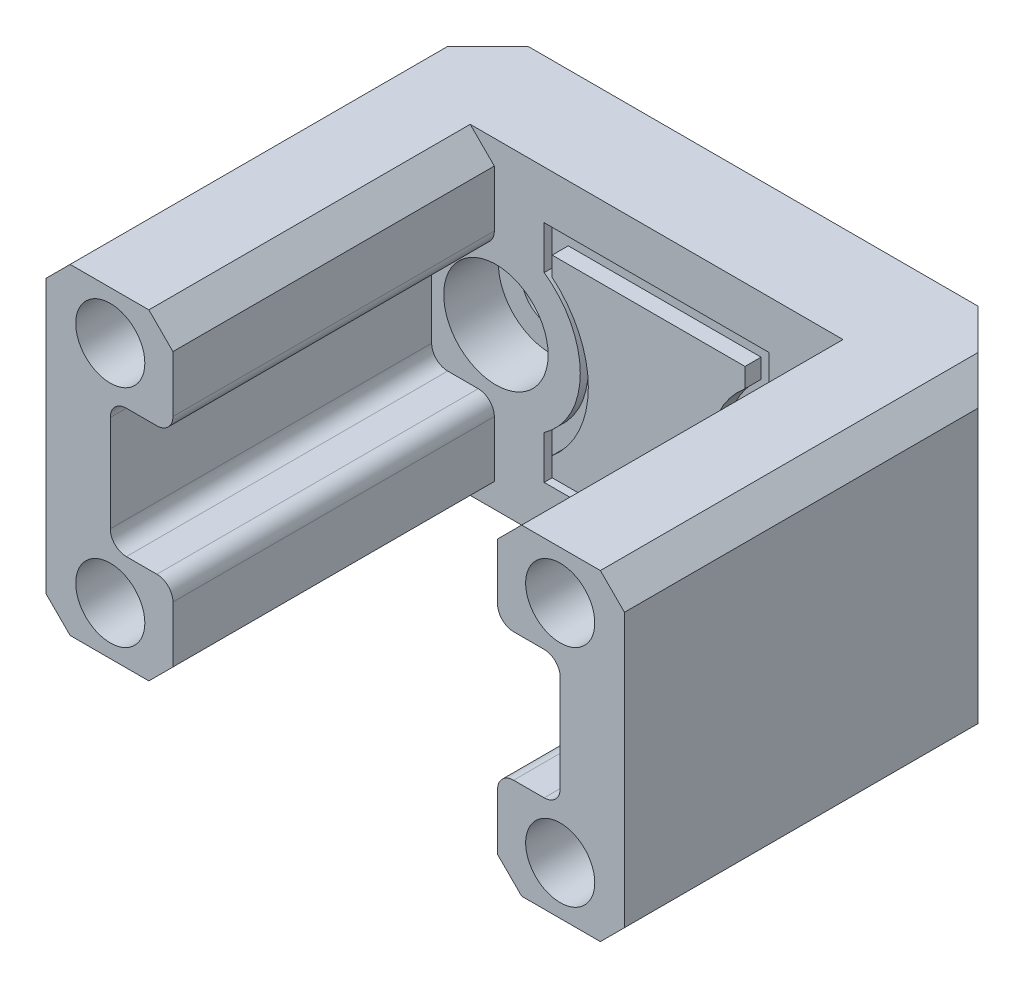
SolidWorks part; units mm, degrees
material "PETG"
ref_plane "Płaszczyzna przednia" through (0, 0, 0) normal (0, 0, 1) x (1, 0, 0)
ref_plane "Płaszczyzna górna" through (0, 0, 0) normal (0, 1, 0) x (1, 0, 0)
ref_plane "Płaszczyzna prawa" through (0, 0, 0) normal (1, 0, 0) x (0, 0, -1)
sketch "Sketch1" plane through (0, 0, 0) normal (0, 0, 1) x (1, 0, 0)
  line L1 (0, 0) -> (28, 0)
  line L2 (0, 0) -> (0, 20)
  line L3 (0, 20) -> (28, 20)
  line L4 (28, 0) -> (28, 20)
  dimension "D1" = 20
  dimension "D2" = 28
extrude "Boss-Extrude1" add sketch "Sketch1" along normal blind 6
hole_wizard "CBORE for M3 Hex Socket Head Cap Screw1" positions "Sketch2" profile "Sketch4" counterbore size "M3" standard "DIN" end condition through all
sketch "Sketch2" plane through (0, 0, 6) normal (0, 0, 1) x (1, 0, 0)
  line L1 (0, 10) -> (4, 10) construction
  line L2 (0, 20) -> (0, 0) construction
  line L3 (4, 10) -> (24, 10) construction
  line L5 (28, 10) -> (24, 10) construction
  line L6 (28, 0) -> (28, 20) construction
  point P0 (4, 10)
  point P2 (24, 10)
  dimension "D1" = 20
sketch "Sketch4" plane through (4, 10, 6) normal (1, 0, 0) x (0, -1, 0)
  line L0 (0, 0) -> (0, 6)
  line L1 (0, 6) -> (1.8, 6)
  line L3 (1.8, 6) -> (1.8, 3.4)
  line L4 (1.8, 3.4) -> (3.25, 3.4)
  line L5 (3.25, 3.4) -> (3.25, 0)
  line L7 (3.25, 0) -> (0, 0)
  line L11 (0, -6.35) -> (0, 107.95) construction
  dimension "Thru Hole Dia." = 3.6
  dimension "Thru Hole Depth" = 6
  dimension "C'Bore Dia." = 6.5
  dimension "C'Bore Depth" = 3.4
sketch "Sketch5" plane through (0, 0, 6) normal (0, 0, 1) x (1, 0, 0)
  line L0 (24.1, 20) -> (24.1, 14)
  line L1 (0, 20) -> (3.9, 20)
  line L2 (0, 20) -> (0, 14)
  line L3 (0, 14) -> (3.9, 14)
  line L4 (3.9, 20) -> (3.9, 14)
  line L9 (24.1, 20) -> (28, 20)
  line L10 (28, 20) -> (28, 14)
  line L11 (24.1, 14) -> (28, 14)
  line L12 (24.1, 6) -> (24.1, 0)
  line L13 (24.1, 6) -> (28, 6)
  line L14 (28, 6) -> (28, 0)
  line L15 (24.1, 0) -> (28, 0)
  line L16 (0, 6) -> (0, 0)
  line L17 (0, 6) -> (3.9, 6)
  line L18 (3.9, 6) -> (3.9, 0)
  line L19 (0, 0) -> (3.9, 0)
  line L20 (28, 0) -> (28, 20) construction
  line L21 (0, 0) -> (28, 0) construction
  dimension "D1" = 20.2
  dimension "D2" = 6
  dimension "D3" = 2
  dimension "D4" = 2
extrude "Boss-Extrude2" add sketch "Sketch5" along normal blind 20
sketch "Sketch6" plane through (0, 0, 0) normal (0, 0, -1) x (-1, 0, 0)
  line L0 (-28, 20) -> (0, 20) construction
  line L1 (-28, 20) -> (-32, 20)
  line L2 (-28, 20) -> (-28, 0)
  line L3 (-28, 0) -> (-32, 0)
  line L4 (-32, 20) -> (-32, 0)
  line L5 (0, 0) -> (4, 0)
  line L6 (0, 0) -> (0, 20)
  line L7 (0, 20) -> (4, 20)
  line L8 (4, 0) -> (4, 20)
  line L9 (0, 0) -> (-28, 0) construction
  dimension "D1" = 4
extrude "Boss-Extrude3" add sketch "Sketch6" against normal up to surface (26 mm away) up to face at (26.05, 17, 26)
fillet "Fillet1" radius 1 8 edges at (0, 14, 16) (0, 6, 16) (28, 14, 16) (28, 6, 16) (3.9, 14, 16) (3.9, 6, 16) (24.1, 14, 16) (24.1, 6, 16)
hole_wizard "Ø4.3 (4.3) Diameter Hole1" positions "Sketch7" profile "Sketch8" hole size "Ø4.3" standard "DIN"
sketch "Sketch7" plane through (0, 0, 26) normal (0, 0, 1) x (1, 0, 0)
  line L1 (-4, 20) -> (0, 20) construction
  line L2 (-4, 20) -> (-4, 17) construction
  line L3 (-4, 17) -> (0, 17) construction
  line L4 (0, 20) -> (0, 17) construction
  line L5 (14, 20) -> (14, 2.3578)
  line L6 (24.1, 20) -> (3.9, 20) construction
  line L8 (-4, 10) -> (16.4891, 10)
  line L9 (-4, 20) -> (-4, 0) construction
  point P1 (0, 17)
  point P60 (0, 3)
  point P62 (28, 3)
  point P63 (28, 17)
  dimension "D1" = 3
  dimension "D2" = 4
sketch "Sketch8" plane through (28, 17, 26) normal (1, 0, 0) x (0, -1, 0)
  line L0 (0, 0) -> (0, 11.2919)
  line L1 (0, 11.2919) -> (2.15, 10)
  line L2 (2.15, 10) -> (2.15, 0)
  line L5 (2.15, 0) -> (0, 0)
  line L10 (0, 11.2919) -> (-2.15, 10) construction
  line L11 (0, -6.35) -> (0, 107.95) construction
  dimension "Hole Dia." = 4.3
  dimension "Hole Depth" = 10
  dimension "Drill Angle" = 118
chamfer "Chamfer1" distance 1.5 angle 45 8 edges at (24.1, 20, 16) (24.1, 0, 16) (3.9, 20, 16) (3.9, 0, 16) (-4, 0, 13) (-4, 20, 13) (32, 0, 13) (32, 20, 13)
sketch "Sketch9" plane through (0, 0, 6) normal (0, 0, 1) x (1, 0, 0)
  line L0 (14, 17) -> (14, 20) construction
  line L1 (7, 17) -> (21, 17)
  line L2 (7, 17) -> (7, 3)
  line L3 (7, 3) -> (21, 3)
  line L4 (21, 17) -> (21, 3)
  line L5 (25.6, 20) -> (2.4, 20) construction
  line L6 (7, 10) -> (-4, 10) construction
  line L7 (-4, 18.5) -> (-4, 1.5) construction
  circle A0 centre (24, 10) radius 3.25 construction
  circle A1 centre (4, 10) radius 3.25 construction
  circle A2 centre (24, 10) radius 3.25
  circle A3 centre (4, 10) radius 3.25
  circle A4 centre (4, 10) radius 5.25
  circle A5 centre (24, 10) radius 5.25
  dimension "D2" = 14
  dimension "D3" = 14
  dimension "D1" = 2
extrude "Cut-Extrude1" cut sketch "Sketch9" against normal blind 0.5 contours A5 L4 L1 L2 A4 L3 region at (14, 10, 6)
sketch "Sketch10" plane through (0, 0, 5.5) normal (0, 0, 1) x (1, 0, 0)
  line L0 (20, 4) -> (20, 5.1977)
  line L1 (8, 4) -> (20, 4)
  line L2 (8, 5.1977) -> (8, 4)
  line L3 (8, 16) -> (8, 14.8023)
  line L4 (20, 16) -> (8, 16)
  line L5 (20, 14.8023) -> (20, 16)
  line L6 (21, 14.3084) -> (21, 17)
  line L7 (21, 17) -> (7, 17)
  line L8 (7, 17) -> (7, 14.3084)
  line L9 (7, 5.6916) -> (7, 3)
  line L10 (7, 3) -> (21, 3)
  line L11 (21, 3) -> (21, 5.6916)
  line L12 (21, 14.3084) -> (21, 17)
  line L13 (21, 17) -> (7, 17)
  line L14 (7, 17) -> (7, 14.3084)
  line L15 (7, 5.6916) -> (7, 3)
  line L16 (7, 3) -> (21, 3)
  line L17 (21, 3) -> (21, 5.6916)
  arc A0 (20, 14.8023) -> (20, 5.1977) centre (24, 10) ccw
  arc A1 (8, 5.1977) -> (8, 14.8023) centre (4, 10) ccw
  arc A2 (21, 14.3084) -> (21, 5.6916) centre (24, 10) ccw
  arc A3 (7, 5.6916) -> (7, 14.3084) centre (4, 10) ccw
  arc A4 (21, 14.3084) -> (21, 5.6916) centre (24, 10) ccw
  arc A5 (7, 5.6916) -> (7, 14.3084) centre (4, 10) ccw
  dimension "D1" = 0
  dimension "D2" = 1
extrude "Boss-Extrude4" add sketch "Sketch10" along normal blind 1 separate body contours A1 L2 L1 L0 A0 L5 L4 L3 region at (14, 10, 5.5)
chamfer "Chamfer3" distance 4 angle 45 2 edges at (-4, 10, 0) (32, 10, 0)
